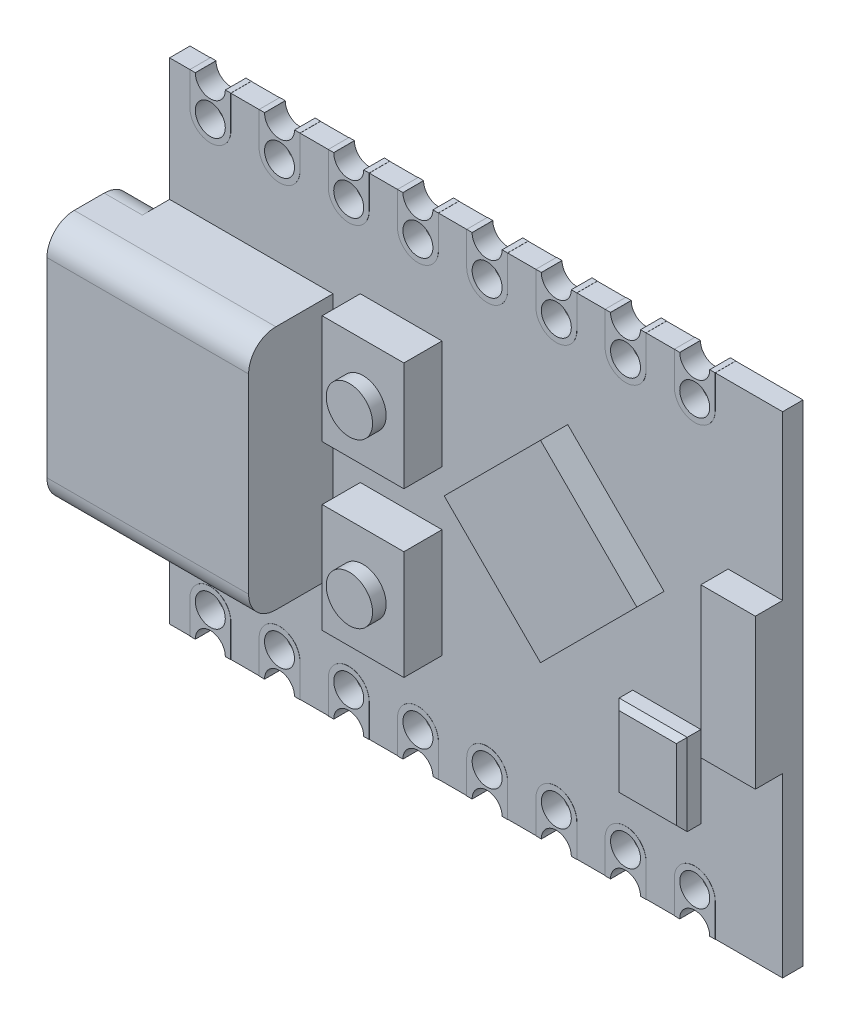
SolidWorks part; units mm, degrees
ref_plane "Plano frontal" through (0, 0, 0) normal (0, 0, 1) x (1, 0, 0)
ref_plane "Plano superior" through (0, 0, 0) normal (0, 1, 0) x (1, 0, 0)
ref_plane "Plano direito" through (0, 0, 0) normal (1, 0, 0) x (0, 0, -1)
sketch "Esboço1" plane through (0, 0, 0) normal (0, 0, 1) x (1, 0, 0)
  line L1 (-22.5, 18) -> (0, 18)
  line L2 (-22.5, 18) -> (-22.5, 0)
  line L3 (-22.5, 0) -> (0, 0)
  line L4 (0, 18) -> (0, 0)
  dimension "D1" = 18
  dimension "D2" = 22.5
extrude "PCI" add sketch "Esboço1" along normal blind 0.75
sketch "Esboço2" plane through (0, 0, 0.75) normal (0, 0, 1) x (1, 0, 0)
  line L0 (-11.4211, 10.1145) -> (-7.8855, 13.65)
  line L1 (-11.4211, 10.1145) -> (-7.8855, 6.5789)
  line L2 (-7.8855, 13.65) -> (-4.35, 10.1145)
  line L3 (-7.8855, 6.5789) -> (-4.35, 10.1145)
  line L4 (0, 0) -> (0, 18) construction
  line L5 (0, 18) -> (-22.5, 18) construction
  dimension "D1" = 45
  dimension "D2" = 4.35
  dimension "D3" = 4.35
  dimension "D4" = 5
extrude "ESP32" add sketch "Esboço2" along normal blind 1
sketch "Esboço3" plane through (0, 0, 0.75) normal (0, 0, 1) x (1, 0, 0)
  line L0 (-22.5, 18) -> (-22.5, 0) construction
  line L1 (-16.5, 13.5) -> (-23.9, 13.5)
  line L2 (-16.5, 13.5) -> (-16.5, 4.5)
  line L3 (-16.5, 4.5) -> (-23.9, 4.5)
  line L4 (-23.9, 13.5) -> (-23.9, 4.5)
  line L5 (-22.5, 9) -> (0, 9) construction
  line L6 (0, 0) -> (0, 18) construction
  dimension "D1" = 1.4
  dimension "D2" = 7.4
  dimension "D3" = 4.5
  dimension "D4" = 9
extrude "USB-C" add sketch "Esboço3" along normal blind 3.1
fillet "Arredondamento inferior USB" radius 1 2 edges at (-23.2, 13.5, 0.75) (-23.2, 4.5, 0.75)
fillet "Arredondamento Superior USB" radius 1 2 edges at (-20.2, 13.5, 3.85) (-20.2, 4.5, 3.85)
sketch "Esboço8" plane through (-23.9, 0, 0) normal (-1, 0, 0) x (0, 0, 1)
  line L0 (1.05, 12.5) -> (1.05, 5.5)
  line L1 (1.75, 4.8) -> (2.85, 4.8)
  line L2 (3.55, 5.5) -> (3.55, 12.5)
  line L3 (2.85, 13.2) -> (1.75, 13.2)
  line L4 (2.85, 13.5) -> (1.75, 13.5) construction
  line L5 (3.85, 12.5) -> (3.85, 5.5) construction
  arc A0 (1.75, 13.2) -> (1.05, 12.5) centre (1.75, 12.5) ccw
  arc A1 (1.05, 5.5) -> (1.75, 4.8) centre (1.75, 5.5) ccw
  arc A2 (2.85, 4.8) -> (3.55, 5.5) centre (2.85, 5.5) ccw
  arc A3 (3.55, 12.5) -> (2.85, 13.2) centre (2.85, 12.5) ccw
  dimension "D1" = 0.7
  dimension "D2" = 0.3
  dimension "D3" = 2.8
  dimension "D4" = 0.3
  dimension "D5" = 8.7
extrude "Furo USB" cut sketch "Esboço8" against normal blind 3.1
sketch "Esboço9" plane through (-23.9, 0, 0) normal (-1, 0, 0) x (0, 0, 1)
  line L0 (2.3, 13.2) -> (2.3, 4.8) construction
  line L1 (2.85, 13.2) -> (1.75, 13.2) construction
  line L2 (1.75, 4.8) -> (2.85, 4.8) construction
  line L3 (1.925, 5.4) -> (2.675, 5.4)
  line L4 (1.925, 5.4) -> (1.925, 12.6)
  line L5 (1.925, 12.6) -> (2.675, 12.6)
  line L6 (2.675, 5.4) -> (2.675, 12.6)
  line L7 (1.925, 5.4) -> (2.675, 12.6) construction
  line L8 (1.925, 12.6) -> (2.675, 5.4) construction
  point P4 (2.3, 9)
  dimension "D1" = 0.6
  dimension "D2" = 0.6
  dimension "D3" = 0.75
extrude "ConexaoUSB" add sketch "Esboço9" against normal up to next from offset 0.5 offset against normal yes
sketch "Esboço10" plane through (0, 0, 0.75) normal (0, 0, 1) x (1, 0, 0)
  line L0 (-22.5, 0) -> (0, 0) construction
  line L1 (-22.5, 4.5) -> (-22.5, 0) construction
  line L2 (-21, 1.2) -> (-21, -0.7241) construction
  line L3 (-21, 16.8) -> (-21, 18.7241) construction
  line L4 (0, 9) -> (-28.3512, 9) construction
  line L5 (0, 0) -> (0, 18) construction
  circle A0 centre (-21, 1.2) radius 0.55
  circle A1 centre (-21, 0) radius 0.55
  circle A2 centre (-18.46, 1.2) radius 0.55
  circle A3 centre (-18.46, 0) radius 0.55
  circle A4 centre (-15.92, 1.2) radius 0.55
  circle A5 centre (-15.92, 0) radius 0.55
  circle A6 centre (-13.38, 1.2) radius 0.55
  circle A7 centre (-13.38, 0) radius 0.55
  circle A8 centre (-10.84, 1.2) radius 0.55
  circle A9 centre (-10.84, 0) radius 0.55
  circle A10 centre (-8.3, 1.2) radius 0.55
  circle A11 centre (-8.3, 0) radius 0.55
  circle A12 centre (-5.76, 1.2) radius 0.55
  circle A13 centre (-5.76, 0) radius 0.55
  circle A14 centre (-3.22, 1.2) radius 0.55
  circle A15 centre (-3.22, 0) radius 0.55
  circle A16 centre (-3.22, 18) radius 0.55
  circle A17 centre (-3.22, 16.8) radius 0.55
  circle A18 centre (-5.76, 18) radius 0.55
  circle A19 centre (-5.76, 16.8) radius 0.55
  circle A20 centre (-8.3, 18) radius 0.55
  circle A21 centre (-8.3, 16.8) radius 0.55
  circle A22 centre (-10.84, 18) radius 0.55
  circle A23 centre (-10.84, 16.8) radius 0.55
  circle A24 centre (-13.38, 18) radius 0.55
  circle A25 centre (-13.38, 16.8) radius 0.55
  circle A26 centre (-15.92, 18) radius 0.55
  circle A27 centre (-15.92, 16.8) radius 0.55
  circle A28 centre (-18.46, 18) radius 0.55
  circle A29 centre (-18.46, 16.8) radius 0.55
  circle A30 centre (-21, 18) radius 0.55
  circle A31 centre (-21, 16.8) radius 0.55
  dimension "D1" = 1.2
  dimension "D2" = 1.1
  dimension "D7" = 2.54
  dimension "D3" = 0
  dimension "D4" = 1.5
  dimension "D5" = 8
extrude "FurosPCB" cut sketch "Esboço10" against normal up to next (0.75 mm away)
sketch "Esboço11" plane through (0, 0, 0.75) normal (0, 0, 1) x (1, 0, 0)
  line L0 (-21.75, 1.2) -> (-21.75, 0)
  line L1 (-20.25, 1.2) -> (-20.25, 0)
  line L2 (-17.71, 1.2) -> (-17.71, 0)
  line L4 (-21.75, 0) -> (-21.55, 0)
  line L5 (-20.45, 0) -> (-20.25, 0)
  line L6 (-17.91, 0) -> (-17.71, 0)
  line L7 (-19.21, 1.2) -> (-19.21, 0)
  line L8 (-19.21, 0) -> (-19.01, 0)
  line L9 (-15.17, 1.2) -> (-15.17, 0)
  line L10 (-15.37, 0) -> (-15.17, 0)
  line L11 (-16.67, 1.2) -> (-16.67, 0)
  line L12 (-16.67, 0) -> (-16.47, 0)
  line L13 (-12.63, 1.2) -> (-12.63, 0)
  line L14 (-12.83, 0) -> (-12.63, 0)
  line L15 (-14.13, 1.2) -> (-14.13, 0)
  line L16 (-14.13, 0) -> (-13.93, 0)
  line L17 (-10.09, 1.2) -> (-10.09, 0)
  line L18 (-10.29, 0) -> (-10.09, 0)
  line L19 (-11.59, 1.2) -> (-11.59, 0)
  line L20 (-11.59, 0) -> (-11.39, 0)
  line L21 (-7.55, 1.2) -> (-7.55, 0)
  line L22 (-7.75, 0) -> (-7.55, 0)
  line L23 (-9.05, 1.2) -> (-9.05, 0)
  line L24 (-9.05, 0) -> (-8.85, 0)
  line L25 (-5.01, 1.2) -> (-5.01, 0)
  line L26 (-5.21, 0) -> (-5.01, 0)
  line L27 (-6.51, 1.2) -> (-6.51, 0)
  line L28 (-6.51, 0) -> (-6.31, 0)
  line L29 (-2.47, 1.2) -> (-2.47, 0)
  line L30 (-2.67, 0) -> (-2.47, 0)
  line L31 (-3.97, 1.2) -> (-3.97, 0)
  line L32 (-3.97, 0) -> (-3.77, 0)
  line L33 (0, 9) -> (-27.4378, 9) construction
  line L34 (0, 0) -> (0, 18) construction
  line L35 (-3.97, 18) -> (-3.77, 18)
  line L36 (-3.97, 16.8) -> (-3.97, 18)
  line L37 (-2.67, 18) -> (-2.47, 18)
  line L38 (-2.47, 16.8) -> (-2.47, 18)
  line L39 (-6.51, 18) -> (-6.31, 18)
  line L40 (-6.51, 16.8) -> (-6.51, 18)
  line L41 (-5.21, 18) -> (-5.01, 18)
  line L42 (-5.01, 16.8) -> (-5.01, 18)
  line L43 (-9.05, 18) -> (-8.85, 18)
  line L44 (-9.05, 16.8) -> (-9.05, 18)
  line L45 (-7.75, 18) -> (-7.55, 18)
  line L46 (-7.55, 16.8) -> (-7.55, 18)
  line L47 (-11.59, 18) -> (-11.39, 18)
  line L48 (-11.59, 16.8) -> (-11.59, 18)
  line L49 (-10.29, 18) -> (-10.09, 18)
  line L50 (-10.09, 16.8) -> (-10.09, 18)
  line L51 (-14.13, 18) -> (-13.93, 18)
  line L52 (-14.13, 16.8) -> (-14.13, 18)
  line L53 (-12.83, 18) -> (-12.63, 18)
  line L54 (-12.63, 16.8) -> (-12.63, 18)
  line L55 (-16.67, 18) -> (-16.47, 18)
  line L56 (-16.67, 16.8) -> (-16.67, 18)
  line L57 (-15.37, 18) -> (-15.17, 18)
  line L58 (-15.17, 16.8) -> (-15.17, 18)
  line L59 (-19.21, 18) -> (-19.01, 18)
  line L60 (-19.21, 16.8) -> (-19.21, 18)
  line L61 (-17.91, 18) -> (-17.71, 18)
  line L62 (-20.45, 18) -> (-20.25, 18)
  line L63 (-21.75, 18) -> (-21.55, 18)
  line L64 (-17.71, 16.8) -> (-17.71, 18)
  line L65 (-20.25, 16.8) -> (-20.25, 18)
  line L66 (-21.75, 16.8) -> (-21.75, 18)
  arc A9 (-20.45, 0) -> (-21.55, 0) centre (-21, 0) ccw construction
  circle A10 centre (-21, 1.2) radius 0.75
  arc A11 (-20.25, 1.2) -> (-21.75, 1.2) centre (-21, 1.2) ccw
  arc A12 (-20.45, 0) -> (-21.55, 0) centre (-21, 0) ccw
  circle A13 centre (-21, 1.2) radius 0.55 construction
  circle A14 centre (-21, 1.2) radius 0.55
  arc A15 (-17.91, 0) -> (-19.01, 0) centre (-18.46, 0) ccw
  circle A16 centre (-18.46, 1.2) radius 0.55
  arc A17 (-17.71, 1.2) -> (-19.21, 1.2) centre (-18.46, 1.2) ccw
  arc A18 (-15.37, 0) -> (-16.47, 0) centre (-15.92, 0) ccw
  circle A19 centre (-15.92, 1.2) radius 0.55
  arc A20 (-15.17, 1.2) -> (-16.67, 1.2) centre (-15.92, 1.2) ccw
  arc A21 (-12.83, 0) -> (-13.93, 0) centre (-13.38, 0) ccw
  circle A22 centre (-13.38, 1.2) radius 0.55
  arc A23 (-12.63, 1.2) -> (-14.13, 1.2) centre (-13.38, 1.2) ccw
  arc A24 (-10.29, 0) -> (-11.39, 0) centre (-10.84, 0) ccw
  circle A25 centre (-10.84, 1.2) radius 0.55
  arc A26 (-10.09, 1.2) -> (-11.59, 1.2) centre (-10.84, 1.2) ccw
  arc A27 (-7.75, 0) -> (-8.85, 0) centre (-8.3, 0) ccw
  circle A28 centre (-8.3, 1.2) radius 0.55
  arc A29 (-7.55, 1.2) -> (-9.05, 1.2) centre (-8.3, 1.2) ccw
  arc A30 (-5.21, 0) -> (-6.31, 0) centre (-5.76, 0) ccw
  circle A31 centre (-5.76, 1.2) radius 0.55
  arc A32 (-5.01, 1.2) -> (-6.51, 1.2) centre (-5.76, 1.2) ccw
  arc A33 (-2.67, 0) -> (-3.77, 0) centre (-3.22, 0) ccw
  circle A34 centre (-3.22, 1.2) radius 0.55
  arc A35 (-2.47, 1.2) -> (-3.97, 1.2) centre (-3.22, 1.2) ccw
  arc A36 (-2.47, 16.8) -> (-3.97, 16.8) centre (-3.22, 16.8) cw
  circle A37 centre (-3.22, 16.8) radius 0.55
  arc A38 (-2.67, 18) -> (-3.77, 18) centre (-3.22, 18) cw
  arc A39 (-5.01, 16.8) -> (-6.51, 16.8) centre (-5.76, 16.8) cw
  circle A40 centre (-5.76, 16.8) radius 0.55
  arc A41 (-5.21, 18) -> (-6.31, 18) centre (-5.76, 18) cw
  arc A42 (-7.55, 16.8) -> (-9.05, 16.8) centre (-8.3, 16.8) cw
  circle A43 centre (-8.3, 16.8) radius 0.55
  arc A44 (-7.75, 18) -> (-8.85, 18) centre (-8.3, 18) cw
  arc A45 (-10.09, 16.8) -> (-11.59, 16.8) centre (-10.84, 16.8) cw
  circle A46 centre (-10.84, 16.8) radius 0.55
  arc A47 (-10.29, 18) -> (-11.39, 18) centre (-10.84, 18) cw
  arc A48 (-12.63, 16.8) -> (-14.13, 16.8) centre (-13.38, 16.8) cw
  circle A49 centre (-13.38, 16.8) radius 0.55
  arc A50 (-12.83, 18) -> (-13.93, 18) centre (-13.38, 18) cw
  arc A51 (-15.17, 16.8) -> (-16.67, 16.8) centre (-15.92, 16.8) cw
  circle A52 centre (-15.92, 16.8) radius 0.55
  arc A53 (-15.37, 18) -> (-16.47, 18) centre (-15.92, 18) cw
  arc A54 (-17.71, 16.8) -> (-19.21, 16.8) centre (-18.46, 16.8) cw
  circle A55 centre (-18.46, 16.8) radius 0.55
  arc A56 (-17.91, 18) -> (-19.01, 18) centre (-18.46, 18) cw
  circle A57 centre (-21, 16.8) radius 0.55
  arc A58 (-20.45, 18) -> (-21.55, 18) centre (-21, 18) cw
  arc A59 (-20.25, 16.8) -> (-21.75, 16.8) centre (-21, 16.8) cw
  dimension "D1" = 0.2
  dimension "D2" = 8
extrude "PADs" add sketch "Esboço11" along normal blind 0.005
sketch "Esboço13" plane through (0, 0, 0) normal (0, 0, -1) x (-1, 0, 0)
  line L0 (22.5, 0) -> (21.55, 0) construction
  line L1 (20.45, 0) -> (19.01, 0) construction
  line L2 (21.75, 0) -> (21.55, 0)
  line L3 (20.45, 0) -> (20.25, 0)
  line L4 (20.25, 1.2) -> (20.25, 0)
  line L5 (21.75, 1.2) -> (21.75, 0)
  line L6 (19.21, 1.2) -> (19.21, 0)
  line L7 (19.21, 0) -> (19.01, 0)
  line L8 (17.91, 0) -> (17.71, 0)
  line L9 (17.71, 1.2) -> (17.71, 0)
  line L10 (16.67, 1.2) -> (16.67, 0)
  line L11 (16.67, 0) -> (16.47, 0)
  line L12 (15.37, 0) -> (15.17, 0)
  line L13 (15.17, 1.2) -> (15.17, 0)
  line L14 (14.13, 1.2) -> (14.13, 0)
  line L15 (14.13, 0) -> (13.93, 0)
  line L16 (12.83, 0) -> (12.63, 0)
  line L17 (12.63, 1.2) -> (12.63, 0)
  line L18 (11.59, 1.2) -> (11.59, 0)
  line L19 (11.59, 0) -> (11.39, 0)
  line L20 (10.29, 0) -> (10.09, 0)
  line L21 (10.09, 1.2) -> (10.09, 0)
  line L22 (9.05, 1.2) -> (9.05, 0)
  line L23 (9.05, 0) -> (8.85, 0)
  line L24 (7.75, 0) -> (7.55, 0)
  line L25 (7.55, 1.2) -> (7.55, 0)
  line L26 (6.51, 1.2) -> (6.51, 0)
  line L27 (6.51, 0) -> (6.31, 0)
  line L28 (5.21, 0) -> (5.01, 0)
  line L29 (5.01, 1.2) -> (5.01, 0)
  line L30 (3.97, 1.2) -> (3.97, 0)
  line L31 (3.97, 0) -> (3.77, 0)
  line L32 (2.67, 0) -> (2.47, 0)
  line L33 (2.47, 1.2) -> (2.47, 0)
  line L34 (0, 9) -> (22.5, 9) construction
  line L35 (0, 0) -> (0, 18) construction
  line L36 (22.5, 18) -> (22.5, 0) construction
  line L37 (2.47, 16.8) -> (2.47, 18)
  line L38 (2.67, 18) -> (2.47, 18)
  line L39 (3.97, 18) -> (3.77, 18)
  line L40 (3.97, 16.8) -> (3.97, 18)
  line L41 (5.01, 16.8) -> (5.01, 18)
  line L42 (5.21, 18) -> (5.01, 18)
  line L43 (6.51, 18) -> (6.31, 18)
  line L44 (6.51, 16.8) -> (6.51, 18)
  line L45 (7.55, 16.8) -> (7.55, 18)
  line L46 (7.75, 18) -> (7.55, 18)
  line L47 (9.05, 18) -> (8.85, 18)
  line L48 (9.05, 16.8) -> (9.05, 18)
  line L49 (10.09, 16.8) -> (10.09, 18)
  line L50 (10.29, 18) -> (10.09, 18)
  line L51 (11.59, 18) -> (11.39, 18)
  line L52 (11.59, 16.8) -> (11.59, 18)
  line L53 (12.63, 16.8) -> (12.63, 18)
  line L54 (12.83, 18) -> (12.63, 18)
  line L55 (14.13, 18) -> (13.93, 18)
  line L56 (14.13, 16.8) -> (14.13, 18)
  line L57 (15.17, 16.8) -> (15.17, 18)
  line L58 (15.37, 18) -> (15.17, 18)
  line L59 (16.67, 18) -> (16.47, 18)
  line L60 (16.67, 16.8) -> (16.67, 18)
  line L61 (17.71, 16.8) -> (17.71, 18)
  line L62 (17.91, 18) -> (17.71, 18)
  line L63 (19.21, 18) -> (19.01, 18)
  line L64 (19.21, 16.8) -> (19.21, 18)
  line L65 (21.75, 16.8) -> (21.75, 18)
  line L66 (20.25, 16.8) -> (20.25, 18)
  line L67 (20.45, 18) -> (20.25, 18)
  line L68 (21.75, 18) -> (21.55, 18)
  circle A0 centre (21, 1.2) radius 0.55 construction
  arc A1 (21.55, 0) -> (20.45, 0) centre (21, 0) ccw construction
  circle A2 centre (21, 1.2) radius 0.55
  arc A3 (21.55, 0) -> (20.45, 0) centre (21, 0) ccw
  arc A4 (21.75, 1.2) -> (20.25, 1.2) centre (21, 1.2) ccw
  circle A5 centre (21, 1.2) radius 0.75 construction
  arc A6 (19.01, 0) -> (17.91, 0) centre (18.46, 0) ccw
  arc A7 (19.21, 1.2) -> (17.71, 1.2) centre (18.46, 1.2) ccw
  circle A8 centre (18.46, 1.2) radius 0.55
  arc A9 (16.47, 0) -> (15.37, 0) centre (15.92, 0) ccw
  arc A10 (16.67, 1.2) -> (15.17, 1.2) centre (15.92, 1.2) ccw
  circle A11 centre (15.92, 1.2) radius 0.55
  arc A12 (13.93, 0) -> (12.83, 0) centre (13.38, 0) ccw
  arc A13 (14.13, 1.2) -> (12.63, 1.2) centre (13.38, 1.2) ccw
  circle A14 centre (13.38, 1.2) radius 0.55
  arc A15 (11.39, 0) -> (10.29, 0) centre (10.84, 0) ccw
  arc A16 (11.59, 1.2) -> (10.09, 1.2) centre (10.84, 1.2) ccw
  circle A17 centre (10.84, 1.2) radius 0.55
  arc A18 (8.85, 0) -> (7.75, 0) centre (8.3, 0) ccw
  arc A19 (9.05, 1.2) -> (7.55, 1.2) centre (8.3, 1.2) ccw
  circle A20 centre (8.3, 1.2) radius 0.55
  arc A21 (6.31, 0) -> (5.21, 0) centre (5.76, 0) ccw
  arc A22 (6.51, 1.2) -> (5.01, 1.2) centre (5.76, 1.2) ccw
  circle A23 centre (5.76, 1.2) radius 0.55
  arc A24 (3.77, 0) -> (2.67, 0) centre (3.22, 0) ccw
  arc A25 (3.97, 1.2) -> (2.47, 1.2) centre (3.22, 1.2) ccw
  circle A26 centre (3.22, 1.2) radius 0.55
  circle A27 centre (3.22, 16.8) radius 0.55
  arc A28 (3.97, 16.8) -> (2.47, 16.8) centre (3.22, 16.8) cw
  arc A29 (3.77, 18) -> (2.67, 18) centre (3.22, 18) cw
  circle A30 centre (5.76, 16.8) radius 0.55
  arc A31 (6.51, 16.8) -> (5.01, 16.8) centre (5.76, 16.8) cw
  arc A32 (6.31, 18) -> (5.21, 18) centre (5.76, 18) cw
  circle A33 centre (8.3, 16.8) radius 0.55
  arc A34 (9.05, 16.8) -> (7.55, 16.8) centre (8.3, 16.8) cw
  arc A35 (8.85, 18) -> (7.75, 18) centre (8.3, 18) cw
  circle A36 centre (10.84, 16.8) radius 0.55
  arc A37 (11.59, 16.8) -> (10.09, 16.8) centre (10.84, 16.8) cw
  arc A38 (11.39, 18) -> (10.29, 18) centre (10.84, 18) cw
  circle A39 centre (13.38, 16.8) radius 0.55
  arc A40 (14.13, 16.8) -> (12.63, 16.8) centre (13.38, 16.8) cw
  arc A41 (13.93, 18) -> (12.83, 18) centre (13.38, 18) cw
  circle A42 centre (15.92, 16.8) radius 0.55
  arc A43 (16.67, 16.8) -> (15.17, 16.8) centre (15.92, 16.8) cw
  arc A44 (16.47, 18) -> (15.37, 18) centre (15.92, 18) cw
  circle A45 centre (18.46, 16.8) radius 0.55
  arc A46 (19.21, 16.8) -> (17.71, 16.8) centre (18.46, 16.8) cw
  arc A47 (19.01, 18) -> (17.91, 18) centre (18.46, 18) cw
  arc A48 (21.75, 16.8) -> (20.25, 16.8) centre (21, 16.8) cw
  arc A49 (21.55, 18) -> (20.45, 18) centre (21, 18) cw
  circle A50 centre (21, 16.8) radius 0.55
  dimension "D1" = 0.2
  dimension "D2" = 8
extrude "InferiorPads" add sketch "Esboço13" along normal blind 0.005
sketch "Esboço14" plane through (0, 18, 0) normal (0, 1, 0) x (1, 0, 0)
  line L0 (-21.75, 0.005) -> (-21.75, -0.755)
  line L1 (-21.75, -0.755) -> (-21.55, -0.755)
  line L2 (-21.55, -0.755) -> (-21.55, 0.005)
  line L3 (-21.55, 0.005) -> (-21.75, 0.005)
  line L4 (-20.45, 0.005) -> (-20.25, 0)
  line L5 (-20.25, 0) -> (-20.25, -0.755)
  line L6 (-20.25, -0.755) -> (-20.45, -0.755)
  line L7 (-20.45, -0.755) -> (-20.45, 0.005)
  line L8 (-19.21, 0.005) -> (-19.21, -0.755)
  line L9 (-19.01, 0.005) -> (-19.21, 0.005)
  line L10 (-19.01, -0.755) -> (-19.01, 0.005)
  line L11 (-19.21, -0.755) -> (-19.01, -0.755)
  line L12 (-17.91, -0.755) -> (-17.91, 0.005)
  line L13 (-17.91, 0.005) -> (-17.71, 0)
  line L14 (-17.71, 0) -> (-17.71, -0.755)
  line L15 (-17.71, -0.755) -> (-17.91, -0.755)
  line L16 (-16.67, 0.005) -> (-16.67, -0.755)
  line L17 (-16.47, 0.005) -> (-16.67, 0.005)
  line L18 (-16.47, -0.755) -> (-16.47, 0.005)
  line L19 (-16.67, -0.755) -> (-16.47, -0.755)
  line L20 (-15.37, -0.755) -> (-15.37, 0.005)
  line L21 (-15.37, 0.005) -> (-15.17, 0)
  line L22 (-15.17, 0) -> (-15.17, -0.755)
  line L23 (-15.17, -0.755) -> (-15.37, -0.755)
  line L24 (-14.13, 0.005) -> (-14.13, -0.755)
  line L25 (-13.93, 0.005) -> (-14.13, 0.005)
  line L26 (-13.93, -0.755) -> (-13.93, 0.005)
  line L27 (-14.13, -0.755) -> (-13.93, -0.755)
  line L28 (-12.83, -0.755) -> (-12.83, 0.005)
  line L29 (-12.83, 0.005) -> (-12.63, 0)
  line L30 (-12.63, 0) -> (-12.63, -0.755)
  line L31 (-12.63, -0.755) -> (-12.83, -0.755)
  line L32 (-11.59, 0.005) -> (-11.59, -0.755)
  line L33 (-11.39, 0.005) -> (-11.59, 0.005)
  line L34 (-11.39, -0.755) -> (-11.39, 0.005)
  line L35 (-11.59, -0.755) -> (-11.39, -0.755)
  line L36 (-10.29, -0.755) -> (-10.29, 0.005)
  line L37 (-10.29, 0.005) -> (-10.09, 0)
  line L38 (-10.09, 0) -> (-10.09, -0.755)
  line L39 (-10.09, -0.755) -> (-10.29, -0.755)
  line L40 (-9.05, 0.005) -> (-9.05, -0.755)
  line L41 (-8.85, 0.005) -> (-9.05, 0.005)
  line L42 (-8.85, -0.755) -> (-8.85, 0.005)
  line L43 (-9.05, -0.755) -> (-8.85, -0.755)
  line L44 (-7.75, -0.755) -> (-7.75, 0.005)
  line L45 (-7.75, 0.005) -> (-7.55, 0)
  line L46 (-7.55, 0) -> (-7.55, -0.755)
  line L47 (-7.55, -0.755) -> (-7.75, -0.755)
  line L48 (-6.51, 0.005) -> (-6.51, -0.755)
  line L49 (-6.31, 0.005) -> (-6.51, 0.005)
  line L50 (-6.31, -0.755) -> (-6.31, 0.005)
  line L51 (-6.51, -0.755) -> (-6.31, -0.755)
  line L52 (-5.21, -0.755) -> (-5.21, 0.005)
  line L53 (-5.21, 0.005) -> (-5.01, 0)
  line L54 (-5.01, 0) -> (-5.01, -0.755)
  line L55 (-5.01, -0.755) -> (-5.21, -0.755)
  line L56 (-3.97, 0.005) -> (-3.97, -0.755)
  line L57 (-3.77, 0.005) -> (-3.97, 0.005)
  line L58 (-3.77, -0.755) -> (-3.77, 0.005)
  line L59 (-3.97, -0.755) -> (-3.77, -0.755)
  line L60 (-2.67, -0.755) -> (-2.67, 0.005)
  line L61 (-2.67, 0.005) -> (-2.47, 0)
  line L62 (-2.47, 0) -> (-2.47, -0.755)
  line L63 (-2.47, -0.755) -> (-2.67, -0.755)
  dimension "D1" = 8
extrude "PADEx" add sketch "Esboço14" along normal blind 0.005
sketch "Esboço16" plane through (0, 0, 0) normal (0, -1, 0) x (1, 0, 0)
  line L0 (-21.75, 0.755) -> (-21.55, 0.755) construction
  line L1 (-21.75, 0.755) -> (-21.55, 0.755)
  line L2 (-21.75, 0.755) -> (-21.75, -0.005)
  line L3 (-21.75, -0.005) -> (-21.55, -0.005)
  line L4 (-21.55, 0.755) -> (-21.55, -0.005)
  line L5 (-20.45, -0.005) -> (-20.25, -0.005)
  line L6 (-20.45, -0.005) -> (-20.45, 0.755)
  line L7 (-20.45, 0.755) -> (-20.25, 0.755)
  line L8 (-20.25, -0.005) -> (-20.25, 0.755)
  line L9 (-21.75, 0.755) -> (-21.75, 0.75) construction
  line L10 (-17.71, -0.005) -> (-17.71, 0.755)
  line L11 (-17.91, -0.005) -> (-17.91, 0.755)
  line L12 (-17.91, -0.005) -> (-17.71, -0.005)
  line L13 (-17.91, 0.755) -> (-17.71, 0.755)
  line L14 (-19.21, 0.755) -> (-19.01, 0.755)
  line L15 (-19.21, 0.755) -> (-19.21, -0.005)
  line L16 (-19.21, -0.005) -> (-19.01, -0.005)
  line L17 (-19.01, 0.755) -> (-19.01, -0.005)
  line L18 (-15.17, -0.005) -> (-15.17, 0.755)
  line L19 (-15.37, -0.005) -> (-15.37, 0.755)
  line L20 (-15.37, -0.005) -> (-15.17, -0.005)
  line L21 (-15.37, 0.755) -> (-15.17, 0.755)
  line L22 (-16.67, 0.755) -> (-16.47, 0.755)
  line L23 (-16.67, 0.755) -> (-16.67, -0.005)
  line L24 (-16.67, -0.005) -> (-16.47, -0.005)
  line L25 (-16.47, 0.755) -> (-16.47, -0.005)
  line L26 (-12.63, -0.005) -> (-12.63, 0.755)
  line L27 (-12.83, -0.005) -> (-12.83, 0.755)
  line L28 (-12.83, -0.005) -> (-12.63, -0.005)
  line L29 (-12.83, 0.755) -> (-12.63, 0.755)
  line L30 (-14.13, 0.755) -> (-13.93, 0.755)
  line L31 (-14.13, 0.755) -> (-14.13, -0.005)
  line L32 (-14.13, -0.005) -> (-13.93, -0.005)
  line L33 (-13.93, 0.755) -> (-13.93, -0.005)
  line L34 (-10.09, -0.005) -> (-10.09, 0.755)
  line L35 (-10.29, -0.005) -> (-10.29, 0.755)
  line L36 (-10.29, -0.005) -> (-10.09, -0.005)
  line L37 (-10.29, 0.755) -> (-10.09, 0.755)
  line L38 (-11.59, 0.755) -> (-11.39, 0.755)
  line L39 (-11.59, 0.755) -> (-11.59, -0.005)
  line L40 (-11.59, -0.005) -> (-11.39, -0.005)
  line L41 (-11.39, 0.755) -> (-11.39, -0.005)
  line L42 (-7.55, -0.005) -> (-7.55, 0.755)
  line L43 (-7.75, -0.005) -> (-7.75, 0.755)
  line L44 (-7.75, -0.005) -> (-7.55, -0.005)
  line L45 (-7.75, 0.755) -> (-7.55, 0.755)
  line L46 (-9.05, 0.755) -> (-8.85, 0.755)
  line L47 (-9.05, 0.755) -> (-9.05, -0.005)
  line L48 (-9.05, -0.005) -> (-8.85, -0.005)
  line L49 (-8.85, 0.755) -> (-8.85, -0.005)
  line L50 (-5.01, -0.005) -> (-5.01, 0.755)
  line L51 (-5.21, -0.005) -> (-5.21, 0.755)
  line L52 (-5.21, -0.005) -> (-5.01, -0.005)
  line L53 (-5.21, 0.755) -> (-5.01, 0.755)
  line L54 (-6.51, 0.755) -> (-6.31, 0.755)
  line L55 (-6.51, 0.755) -> (-6.51, -0.005)
  line L56 (-6.51, -0.005) -> (-6.31, -0.005)
  line L57 (-6.31, 0.755) -> (-6.31, -0.005)
  line L58 (-2.47, -0.005) -> (-2.47, 0.755)
  line L59 (-2.67, -0.005) -> (-2.67, 0.755)
  line L60 (-2.67, -0.005) -> (-2.47, -0.005)
  line L61 (-2.67, 0.755) -> (-2.47, 0.755)
  line L62 (-3.97, 0.755) -> (-3.77, 0.755)
  line L63 (-3.97, 0.755) -> (-3.97, -0.005)
  line L64 (-3.97, -0.005) -> (-3.77, -0.005)
  line L65 (-3.77, 0.755) -> (-3.77, -0.005)
  dimension "D1" = 8
extrude "PADEx1" add sketch "Esboço16" along normal blind 0.005
sketch "Esboço17" plane through (0, 0, 0.75) normal (0, 0, 1) x (1, 0, 0)
  line L0 (0, 18) -> (-2.47, 18) construction
  line L1 (-2, 12) -> (0, 12)
  line L2 (-2, 12) -> (-2, 6.5)
  line L3 (-2, 6.5) -> (0, 6.5)
  line L4 (0, 12) -> (0, 6.5)
  line L5 (0, 0) -> (0, 18) construction
  dimension "D1" = 6
  dimension "D2" = 5.5
  dimension "D3" = 2
extrude "Antena" add sketch "Esboço17" along normal blind 1
sketch "Esboço18" plane through (0, 0, 0.75) normal (0, 0, 1) x (1, 0, 0)
  line L0 (-16.5, 4.5) -> (-16.5, 13.5) construction
  line L1 (-15.5, 14) -> (-12.5, 14)
  line L2 (-15.5, 14) -> (-15.5, 10)
  line L3 (-15.5, 10) -> (-12.5, 10)
  line L4 (-12.5, 14) -> (-12.5, 10)
  line L5 (-15.5, 8) -> (-12.5, 8)
  line L6 (-15.5, 8) -> (-15.5, 4)
  line L7 (-15.5, 4) -> (-12.5, 4)
  line L8 (-12.5, 8) -> (-12.5, 4)
  line L9 (-14.13, 18) -> (-15.17, 18) construction
  point P8 (-16.5, 9)
  dimension "D1" = 4
  dimension "D2" = 3
  dimension "D3" = 1
  dimension "D4" = 2
  dimension "D5" = 8
extrude "Buttons" add sketch "Esboço18" along normal blind 1.4
sketch "Esboço19" plane through (0, 0, 2.15) normal (0, 0, 1) x (1, 0, 0)
  line L0 (-12.5, 10) -> (-12.5, 14) construction
  line L2 (-12.5, 14) -> (-15.5, 14) construction
  line L4 (-12.5, 8) -> (-15.5, 8) construction
  line L5 (-12.5, 4) -> (-12.5, 8) construction
  circle A0 centre (-14, 6) radius 0.85
  circle A1 centre (-14, 12) radius 0.85
  dimension "D1" = 1.7
  dimension "D2" = 1.5
  dimension "D3" = 2
  dimension "D4" = 2
  dimension "D5" = 1.5
extrude "Ressalto-extrusão12" add sketch "Esboço19" along normal blind 0.5
sketch "Esboço20" plane through (0, 0, 0.75) normal (0, 0, 1) x (1, 0, 0)
  line L0 (-5.01, 0) -> (-3.97, 0) construction
  line L1 (-5.5, 6.4) -> (-3, 6.4)
  line L2 (-5.5, 6.4) -> (-5.5, 3.4)
  line L3 (-5.5, 3.4) -> (-3, 3.4)
  line L4 (-3, 6.4) -> (-3, 3.4)
  line L5 (0, 0) -> (0, 6.5) construction
  dimension "D1" = 3
  dimension "D2" = 2.5
  dimension "D3" = 3.4
  dimension "D4" = 3
extrude "Ressalto-extrusão13" add sketch "Esboço20" along normal blind 0.7
chamfer "Chanfro1" distance 0.2 angle 45 4 edges at (-4.25, 6.4, 1.45) (-3, 4.9, 1.45) (-4.25, 3.4, 1.45) (-5.5, 4.9, 1.45)
